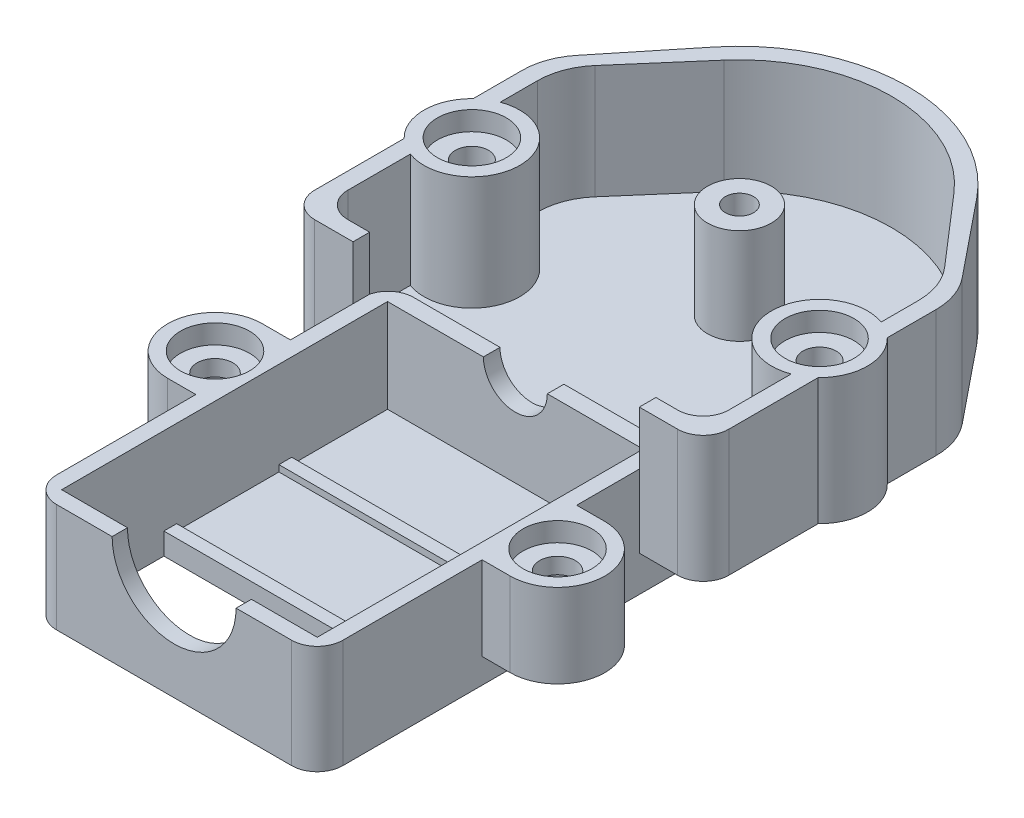
SolidWorks part; units mm, degrees
ref_plane "Alzado" through (0, 0, 0) normal (0, 0, 1) x (1, 0, 0)
ref_plane "Planta" through (0, 0, 0) normal (0, 1, 0) x (1, 0, 0)
ref_plane "Vista lateral" through (0, 0, 0) normal (1, 0, 0) x (0, 0, -1)
sketch "Croquis1" plane through (0, 0, 0) normal (0, 1, 0) x (1, 0, 0)
  line L4 (0, 0) -> (0, 27.5)
  line L5 (0, 27.5) -> (22.4, 27.5)
  line L6 (22.4, 27.5) -> (22.4, 0)
  line L7 (22.4, 0) -> (0, 0)
  dimension "D1" = 27.5
  dimension "D2" = 22.4
extrude "Saliente-Extruir3" add sketch "Croquis1" along normal blind 8.5
shell "Vaciado5" thickness 1.2 removed face at (11.2, 8.5, -13.75)
sketch "Croquis9" plane through (0, 0, 0) normal (0, 0, 1) x (1, 0, 0)
  line L0 (0, 8.5) -> (22.4, 8.5) construction
  line L1 (6.35, 8.5) -> (16.05, 8.5)
  arc A0 (6.35, 8.5) -> (16.05, 8.5) centre (11.2, 8.5) ccw
  dimension "D1" = 9.7
extrude "Cortar-Extruir8" cut sketch "Croquis9" against normal up to next
sketch "Croquis10" plane through (0, 1.2, 0) normal (0, 1, 0) x (1, 0, 0)
  line L0 (1.2, 1.2) -> (1.2, 9.2)
  line L1 (1.2, 26.3) -> (1.2, 1.2) construction
  line L2 (1.2, 9.2) -> (21.2, 9.2)
  line L3 (21.2, 1.2) -> (21.2, 26.3) construction
  line L4 (21.2, 9.2) -> (21.2, 1.2)
  line L5 (21.2, 1.2) -> (1.2, 1.2)
  dimension "D1" = 8
extrude "Cortar-Extruir9" cut sketch "Croquis10" against normal up to next
sketch "Croquis11" plane through (0, 1.2, 0) normal (0, 1, 0) x (1, 0, 0)
  line L0 (1.2, 9.2) -> (21.2, 9.2)
  line L1 (21.2, 9.2) -> (21.2, 10.2)
  line L2 (21.2, 9.2) -> (21.2, 26.3) construction
  line L3 (21.2, 10.2) -> (1.2, 10.2)
  line L4 (1.2, 26.3) -> (1.2, 9.2) construction
  line L5 (1.2, 10.2) -> (1.2, 9.2)
  line L6 (1.2, 10.2) -> (1.2, 18.2)
  line L7 (1.2, 18.2) -> (21.2, 18.2)
  line L8 (21.2, 1.2) -> (21.2, 26.3) construction
  line L9 (21.2, 18.2) -> (21.2, 19.2)
  line L10 (21.2, 19.2) -> (1.2, 19.2)
  line L11 (1.2, 26.3) -> (1.2, 1.2) construction
  line L12 (1.2, 19.2) -> (1.2, 18.2)
  line M6 (1.2, 9.2) -> (21.2, 9.2)
  line M7 (21.2, 9.2) -> (21.2, 26.3)
  line M9 (1.2, 26.3) -> (1.2, 9.2)
  dimension "D1" = 1
  dimension "D2" = 8
extrude "Saliente-Extruir4" add sketch "Croquis11" along normal blind 0.5 contours L10 L7 M7 M9 | L3 M7 M9 M6 region at (11.2, 1.2, -9.7) region at (11.2, 1.2, -18.7)
sketch "Croquis12" plane through (0, 0, -27.5) normal (0, 0, -1) x (-1, 0, 0)
  line L0 (-22.4, 8.5) -> (0, 8.5) construction
  line L1 (-13.7, 8.5) -> (-8.7, 8.5)
  arc A0 (-13.7, 8.5) -> (-8.7, 8.5) centre (-11.2, 8.5) ccw
  dimension "D1" = 5
extrude "Cortar-Extruir10" cut sketch "Croquis12" against normal up to next contours A0 L1
sketch "Croquis15" plane through (0, 0, 0) normal (0, -1, 0) x (1, 0, 0)
  line L0 (22.4, -27.5) -> (22.4, -25.2)
  line L1 (22.4, 0) -> (22.4, -27.5) construction
  line L2 (22.4, -25.2) -> (27.4, -25.2)
  line L3 (0, -25.2) -> (-5, -25.2)
  line L4 (0, -27.5) -> (0, 0) construction
  line L5 (0, -25.2) -> (22.4, -25.2) construction
  line L6 (11.2, -25.2) -> (11.2, -57.5)
  line L7 (-5, -25.2) -> (-5, -57.5)
  line L8 (-5, -57.5) -> (27.4, -57.5)
  line L9 (27.4, -57.5) -> (27.4, -25.2)
  line L11 (0, -25.2) -> (0, -27.5)
  line L12 (0, -27.5) -> (22.4, -27.5)
  line M10 (0, 0) -> (0, -27.5)
  line M11 (0, -27.5) -> (22.4, -27.5)
  line M12 (22.4, -27.5) -> (22.4, 0)
  dimension "D1" = 2.3
  dimension "D2" = 5
  dimension "D3" = 5
  dimension "D4" = 32.3
extrude "Saliente-Extruir7" add sketch "Croquis15" against normal blind 12.7 contours L7 L8 L6 L3 M11 M10 | L8 L9 L2 L6 M12 M11 region at (19.4294, 0, -42.1267) region at (2.9706, 0, -42.1267)
sketch "Croquis16" plane through (0, 0, 0) normal (0, -1, 0) x (1, 0, 0)
  line L0 (0, -25.2) -> (-5, -25.2)
  line L1 (-5, -25.2) -> (-5, -57.5)
  line L2 (-5, -57.5) -> (27.4, -57.5)
  line L3 (27.4, -57.5) -> (27.4, -25.2)
  line L4 (27.4, -25.2) -> (22.4, -25.2)
  line L5 (22.4, -25.2) -> (22.4, -28.2)
  line L6 (22.4, -28.2) -> (0, -28.2)
  line L7 (0, -28.2) -> (0, -25.2)
  dimension "D1" = 3
extrude "Cortar-Extruir11" cut sketch "Croquis16" against normal blind 2.8 contours L7 L0 L1 L2 L3 L4 L5 L6
sketch "Croquis17" plane through (0, 12.7, 0) normal (0, 1, 0) x (1, 0, 0)
  line L0 (27.4, 25.2) -> (27.4, 45.2)
  line L1 (27.4, 57.5) -> (27.4, 25.2) construction
  line L3 (-5, 25.2) -> (-5, 57.5) construction
  line L4 (11.2, 57.5) -> (11.2, 30.968) construction
  line L5 (-5, 57.5) -> (27.4, 57.5) construction
  line L6 (27.4, 45.2) -> (21.4604, 52.5385)
  line L7 (-5, 45.2) -> (0.9396, 52.5385)
  line L8 (8.7, 27.5) -> (13.7, 27.5) construction
  line L9 (-5, 45.2) -> (-5, 57.5)
  line L10 (-5, 57.5) -> (27.4, 57.5)
  line L11 (27.4, 57.5) -> (27.4, 45.2)
  arc A0 (21.4604, 52.5385) -> (0.9396, 52.5385) centre (11.2, 44.234) ccw
  point P18 (11.2, 27.5)
  line M7 (-5, 57.5) -> (-5, 25.2)
  line M13 (27.4, 25.2) -> (27.4, 57.5)
  line M14 (27.4, 57.5) -> (-5, 57.5)
  dimension "D2" = 26.4
  dimension "D1" = 20
  dimension "D3" = 16.734
extrude "Cortar-Extruir12" cut sketch "Croquis17" against normal up to next contours L4 L10 L7 A0 M7 | L4 A0 L6 M14 M13 region at (23.4362, 12.7, -53.6752) region at (-1.0362, 12.7, -53.6752)
sketch "Croquis19" plane through (0, 12.7, 0) normal (0, 1, 0) x (1, 0, 0)
  line L0 (11.2, 57.434) -> (11.2, 56.134) construction
  line L1 (24.9, 25.2) -> (24.9, 26.5) construction
  line L2 (0, 26.5) -> (0, 27.5)
  line L3 (-5, 32.73) -> (-3.7, 32.73) construction
  line L4 (-5, 25.2) -> (-5, 45.2) construction
  line L5 (22.4, 25.2) -> (27.4, 25.2) construction
  line L6 (0, 25.2) -> (0, 27.5) construction
  line L7 (0, 26.5) -> (-3.7, 26.5)
  line L8 (-3.7, 26.5) -> (-3.7, 42.9559)
  line L9 (27.4, 32.73) -> (26.1, 32.73) construction
  line L10 (27.4, 45.2) -> (27.4, 25.2) construction
  line L11 (22.4, 26.5) -> (26.1, 26.5)
  line L12 (22.4, 27.5) -> (22.4, 25.2) construction
  line L13 (26.1, 26.5) -> (26.1, 43.1356)
  line L16 (0, 27.5) -> (22.4, 27.5)
  line L17 (22.4, 27.5) -> (22.4, 26.5)
  line L18 (-3.7, 42.9559) -> (-3.7, 45.2)
  line L19 (-3.7, 45.2) -> (2.2008, 52.0201)
  line L20 (26.1, 43.1356) -> (26.1, 45.2)
  line L21 (26.1, 45.2) -> (20.1992, 52.0201)
  line L22 (-5, 45.2) -> (-1.1318, 45.2) construction
  line L23 (-1.1318, 45.2) -> (32.1711, 45.2) construction
  arc A1 (21.4604, 52.5385) -> (0.9396, 52.5385) centre (11.2, 44.234) ccw construction
  arc A2 (20.1992, 52.0201) -> (2.2008, 52.0201) centre (11.2, 44.234) ccw
  dimension "D1" = 1.3
  dimension "D2" = 1.3
  dimension "D3" = 1.3
  dimension "D4" = 1.3
  dimension "D5" = 18.7
  dimension "D6" = 18.7
extrude "Cortar-Extruir13" cut sketch "Croquis19" against normal blind 8.9
sketch "Croquis20" plane through (0, 0, -27.5) normal (0, 0, -1) x (-1, 0, 0)
  line L0 (0, 8.5) -> (0, 3.8)
  line L1 (0, 3.8) -> (0, 8.5) construction
  line L2 (0, 3.8) -> (-22.4, 3.8) construction
  line L3 (0, 3.8) -> (-22.4, 3.8)
  line L4 (-22.4, 3.8) -> (-22.4, 8.5)
  line L5 (-22.4, 8.5) -> (-13.7, 8.5)
  line L6 (-8.7, 8.5) -> (0, 8.5)
  arc A0 (-13.7, 8.5) -> (-8.7, 8.5) centre (-11.2, 8.5) ccw
extrude "Saliente-Extruir8" add sketch "Croquis20" along normal blind 0.5
sketch "Croquis22" plane through (0, 0, -26.3) normal (0, 0, 1) x (1, 0, 0)
  line L0 (1.2, 8.5) -> (8.7, 8.5)
  line L2 (13.7, 8.5) -> (21.2, 8.5)
  line L3 (21.2, 8.5) -> (21.2, 1.2)
  line L4 (21.2, 1.2) -> (1.2, 1.2)
  line L5 (1.2, 1.2) -> (1.2, 8.5)
  arc A0 (8.7, 8.5) -> (13.7, 8.5) centre (11.2, 8.5) ccw
extrude "Cortar-Extruir14" cut sketch "Croquis22" against normal blind 0.4
sketch "Croquis23" plane through (0, 3.8, 0) normal (0, 1, 0) x (1, 0, 0)
  circle A0 centre (11.2, 44.234) radius 2.5
  circle A1 centre (11.2, 44.234) radius 1.1
  dimension "D1" = 2.2
  dimension "D2" = 5
extrude "Saliente-Extruir10" add sketch "Croquis23" along normal blind 7.5 contours A0 | A1
sketch "Croquis24" plane through (0, 12.7, 0) normal (0, 1, 0) x (1, 0, 0)
  line L0 (26.1, 26.5) -> (26.1, 45.2) construction
  line L1 (24.8, 35.6) -> (24.8, 36.9) construction
  line L2 (22.4, 25.2) -> (27.4, 25.2) construction
  line L3 (-3.7, 45.2) -> (-3.7, 26.5) construction
  circle A0 centre (24.8, 36.9) radius 1.3
  circle A1 centre (24.8, 36.9) radius 3.75
  circle A2 centre (-2.4, 36.9) radius 1.3
  circle A3 centre (-2.4, 36.9) radius 3.75
  dimension "D1" = 2.6
  dimension "D3" = 7.5
  dimension "D2" = 10.4
extrude "Saliente-Extruir11" add sketch "Croquis24" against normal up to vertex (9.9 mm away) up to point (27.4, 2.8, -45.2)
sketch "Croquis25" plane through (0, 3.8, 0) normal (0, 1, 0) x (1, 0, 0)
  circle A0 centre (24.8, 36.9) radius 1.3
  circle A1 centre (-2.4, 36.9) radius 1.3
extrude "Cortar-Extruir18" cut sketch "Croquis25" against normal up to next
sketch "Croquis26" plane through (0, 12.7, 0) normal (0, 1, 0) x (1, 0, 0)
  circle A0 centre (24.8, 36.9) radius 2.7
  circle A1 centre (-2.4, 36.9) radius 2.7
  dimension "D1" = 5.4
extrude "Cortar-Extruir19" cut sketch "Croquis26" against normal blind 1.5
sketch "Croquis27" plane through (0, 2.8, 0) normal (0, -1, 0) x (1, 0, 0)
  circle A0 centre (-2.4, -36.9) radius 2.45
  circle A1 centre (24.8, -36.9) radius 2.45
  dimension "D1" = 4.9
extrude "Cortar-Extruir20" cut sketch "Croquis27" against normal blind 6.5
sketch "Croquis29" plane through (0, 8.5, 0) normal (0, 1, 0) x (1, 0, 0)
  line L0 (24.25, 26.5) -> (24.25, 19.3) construction
  line L1 (22.4, 26.5) -> (26.1, 26.5) construction
  line L2 (21.2, 14.2) -> (21.9, 14.2) construction
  line L3 (21.2, 10.2) -> (21.2, 18.2) construction
  line L4 (21.9, 14.2) -> (21.9, 19.7435) construction
  line L5 (24.6, 16.6) -> (24.6, 19.3) construction
  line L6 (24.6, 20.3) -> (22.4, 20.3)
  line L7 (22.4, 0) -> (22.4, 25.2) construction
  line L9 (22.4, 12.9) -> (24.6, 12.9)
  line L10 (22.4, 20.3) -> (21.2, 20.3)
  line L11 (21.2, 1.2) -> (21.2, 26.7) construction
  line L12 (21.2, 20.3) -> (21.2, 12.9)
  line L13 (21.2, 12.9) -> (22.4, 12.9)
  arc A1 (24.6, 12.9) -> (24.25, 20.2834) centre (24.6, 16.6) ccw
  circle A2 centre (24.6, 16.6) radius 1.4
  line M8 (21.2, 26.7) -> (21.2, 1.2)
  line M12 (22.4, 0) -> (22.4, 25.2)
  dimension "D4" = 7.4
  dimension "D1" = 7.2
  dimension "D2" = 0.7
extrude "Saliente-Extruir12" add sketch "Croquis29" against normal blind 6.55 contours L9 A1 L6 A2 M12 | L13 L10 M8 M12 region at (28.2054, 8.5, -16.6) region at (21.8, 8.5, -16.6)
sketch "Croquis30" plane through (0, 8.5, 0) normal (0, 1, 0) x (1, 0, 0)
  circle A0 centre (24.6, 16.6) radius 2.7
  dimension "D1" = 5.4
extrude "Cortar-Extruir21" cut sketch "Croquis30" against normal blind 1.5
sketch "Croquis31" plane through (0, 1.95, 0) normal (0, -1, 0) x (1, 0, 0)
  circle A0 centre (24.6, -16.6) radius 2.425
  dimension "D1" = 4.85
extrude "Cortar-Extruir22" cut sketch "Croquis31" against normal blind 3.8
sketch "Croquis32" plane through (0, 0, 0) normal (0, -1, 0) x (1, 0, 0)
  line L0 (22.4, -15.5799) -> (22.4, -17.6201)
  arc A0 (22.4, -15.5799) -> (22.4, -17.6201) centre (24.6, -16.6) ccw
extrude "Cortar-Extruir23" cut sketch "Croquis32" against normal blind 3.8
ref_axis "Eje2" through (11.2, 1.7, -18.2) along (0, -0.0624, 0.9981)
sketch "Croquis37" plane through (0, 8.5, 0) normal (0, 1, 0) x (1, 0, 0)
  line L0 (22.4, 20.3) -> (21.2, 20.3) construction
  line L1 (22.4, 12.9) -> (21.2, 12.9) construction
  line L2 (24.6, 16.6) -> (21.2, 16.6) construction
  line L4 (1.2, 16.6) -> (-2.2, 16.6) construction
  line L7 (1.2, 12.9) -> (1.2, 20.3)
  line L8 (1.2, 18.2) -> (1.2, 10.2) construction
  line L9 (24.6, 12.9) -> (21.2, 12.9) construction
  line L10 (21.2, 10.3267) -> (21.2, 21.7036) construction
  line L11 (21.2, 1.2) -> (21.2, 26.7) construction
  line L12 (1.2, 26.7) -> (1.2, 19.2) construction
  line L13 (-2.2, 12.9) -> (1.2, 12.9)
  line L14 (1.2, 20.3) -> (-2.2, 20.3)
  arc A0 (-2.2, 20.3) -> (-2.2, 12.9) centre (-2.2, 16.6) ccw
  arc A1 (24.6, 12.9) -> (24.6, 20.3) centre (24.6, 16.6) ccw construction
  circle A2 centre (-2.2, 16.6) radius 1.4
  circle A3 centre (24.6, 16.6) radius 1.4 construction
extrude "Saliente-Extruir16" add sketch "Croquis37" against normal blind 6.55
sketch "Croquis41" plane through (0, 8.5, 0) normal (0, 1, 0) x (1, 0, 0)
  circle A0 centre (-2.2, 16.6) radius 2.7
  circle A1 centre (24.6, 16.6) radius 2.7 construction
extrude "Cortar-Extruir25" cut sketch "Croquis41" against normal up to surface (1.5 mm away) up to face at (24.6, 7, -13.9)
sketch "Croquis42" plane through (0, 1.95, 0) normal (0, -1, 0) x (1, 0, 0)
  circle A0 centre (-2.2, -16.6) radius 2.425
  arc A1 (22.4, -17.6201) -> (22.4, -15.5799) centre (24.6, -16.6) ccw construction
extrude "Cortar-Extruir26" cut sketch "Croquis42" against normal up to surface (3.8 mm away) up to face at (24.6, 5.75, -19.025)
sketch "Croquis43" plane through (0, 0, 0) normal (0, -1, 0) x (1, 0, 0)
  line L0 (0, -15.6757) -> (0, -17.5243)
  arc A0 (0, -17.5243) -> (0, -15.6757) centre (-2.2, -16.6) ccw
extrude "Cortar-Extruir27" cut sketch "Croquis43" against normal up to surface (5.75 mm away) contours A0 L0 up to face at (24.6, 5.75, -19.025)
fillet "Redondeo2" radius 5 4 edges at (-5, 7.75, -45.2) (-3.7, 8.25, -45.2) (26.1, 8.25, -45.2) (27.4, 7.75, -45.2)
fillet "Redondeo3" radius 2 8 edges at (0, 4.25, 0) (22.4, 4.25, 0) (0, 6.15, -28) (22.4, 6.15, -28) (-3.7, 8.25, -26.5) (-5, 7.75, -25.2) (26.1, 8.25, -26.5) (27.4, 7.75, -25.2)
